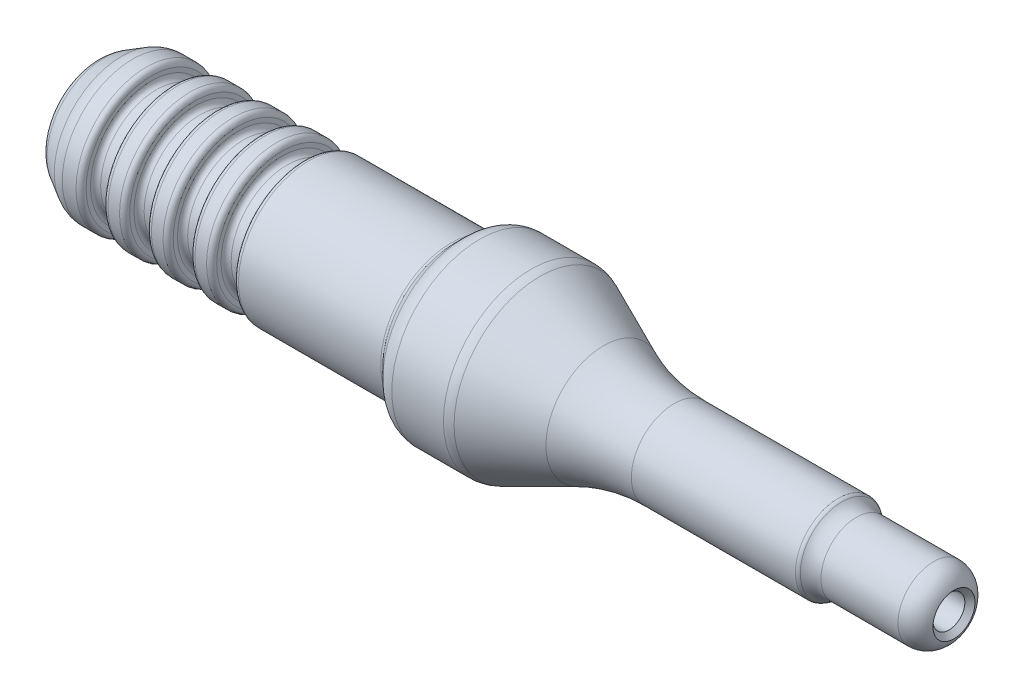
SolidWorks part; units mm, degrees
material "Seramik Porselen"
ref_plane "Ön Düzlem" through (0, 0, 0) normal (0, 0, 1) x (1, 0, 0)
ref_plane "Üst Düzlem" through (0, 0, 0) normal (0, 1, 0) x (1, 0, 0)
ref_plane "Sağ Düzlem" through (0, 0, 0) normal (1, 0, 0) x (0, 0, -1)
sketch "Çizim1" plane through (0, 0, 0) normal (0, 0, 1) x (1, 0, 0)
  line L0 (0, 0) -> (0, 3.52)
  line L1 (0, 3.52) -> (2.3, 4.8479)
  line L2 (2.3, 4.8479) -> (24.8, 4.8479)
  line L3 (24.8, 4.8479) -> (26, 6.0479)
  line L4 (26, 6.0479) -> (30.5, 6.0479)
  line L5 (30.5, 6.0479) -> (37.5, 2.9474)
  line L6 (37.5, 2.9474) -> (51.5, 2.9474)
  line L7 (51.5, 2.9474) -> (51.7872, 2.45)
  line L8 (51.7872, 2.45) -> (59.3372, 2.45)
  line L9 (59.3372, 2.45) -> (59.3372, 0)
  line L10 (59.3372, 0) -> (0, 0)
  dimension "D1" = 3.52
  dimension "D2" = 30
  dimension "D3" = 2.3
  dimension "D4" = 22.5
  dimension "D5" = 45
  dimension "D6" = 1.2
  dimension "D7" = 4.5
  dimension "D8" = 156.11
  dimension "D9" = 7
  dimension "D10" = 120
  dimension "D11" = 14
  dimension "D12" = 2.45
  dimension "D13" = 7.55
revolve "Döndür1" add sketch "Çizim1" angle 360 about L10
sketch "Çizim2" plane through (0, 0, 0) normal (0, 0, 1) x (1, 0, 0)
  line L0 (0, 0) -> (0, 2.7)
  line L1 (0, 3.52) -> (0, -3.52) construction
  line L2 (0, 2.7) -> (33.5, 2.7)
  line L3 (33.5, 2.7) -> (36.2713, 1.1)
  line L4 (36.2713, 1.1) -> (59.3372, 1.1)
  line L5 (59.3372, -2.45) -> (59.3372, 2.45) construction
  line L6 (59.3372, 1.1) -> (59.3372, 0)
  line L7 (59.3372, 0) -> (0, 0)
  line L8 (7, 3.85) -> (7, 4.85)
  line L9 (4, 3.85) -> (5.5, 3.85)
  line L10 (4, 3.85) -> (4, 4.85)
  line L11 (4, 4.85) -> (5.5, 4.85)
  line L12 (5.5, 3.85) -> (5.5, 4.85)
  line L13 (7, 3.85) -> (8.5, 3.85)
  line L14 (8.5, 3.85) -> (8.5, 4.85)
  line L15 (7, 4.85) -> (8.5, 4.85)
  line L16 (10, 3.85) -> (10, 4.85)
  line L17 (10, 3.85) -> (11.5, 3.85)
  line L18 (11.5, 3.85) -> (11.5, 4.85)
  line L19 (10, 4.85) -> (11.5, 4.85)
  line L20 (13, 3.85) -> (13, 4.85)
  line L21 (13, 3.85) -> (14.5, 3.85)
  line L22 (14.5, 3.85) -> (14.5, 4.85)
  line L23 (13, 4.85) -> (14.5, 4.85)
  dimension "D1" = 2.7
  dimension "D2" = 150
  dimension "D3" = 33.5
  dimension "D4" = 1.1
  dimension "D5" = 1
  dimension "D6" = 1.5
  dimension "D7" = 4
  dimension "D8" = 4.85
  dimension "D10" = 1.5
  dimension "D9" = 4
revolve "Kes-Döndür1" cut sketch "Çizim2" angle 360 about L7
fillet "Radyus1" radius 12 1 edges at (37.5, 0, -2.9474)
chamfer "Pah1" distance 0.35 angle 45 1 edges at (59.3372, 0, -1.1)
fillet "Radyus2" radius 1.5 6 edges at (2.3, 0, -4.8479) (0, 0, -3.52) (26, 0, -6.0479) (30.5, 0, -6.0479) (59.3372, 0, -2.45) (51.7872, 0, -2.45)
fillet "Radyus3" radius 0.35 18 edges at (14.5, 0, -3.85) (14.5, 0, -4.8479) (13, 0, -3.85) (13, 0, 4.8479) (11.5, 0, -3.85) (11.5, 0, -4.8479) (10, 0, -3.85) (10, 0, 4.8479) (8.5, 0, -3.85) (8.5, 0, -4.8479) (7, 0, -3.85) (7, 0, 4.8479) (4, 0, -3.85) (4, 0, 4.8479) (5.5, 0, -3.85) (5.5, 0, -4.8479) (51.5, 0, -2.9474) (24.8, 0, -4.8479)
